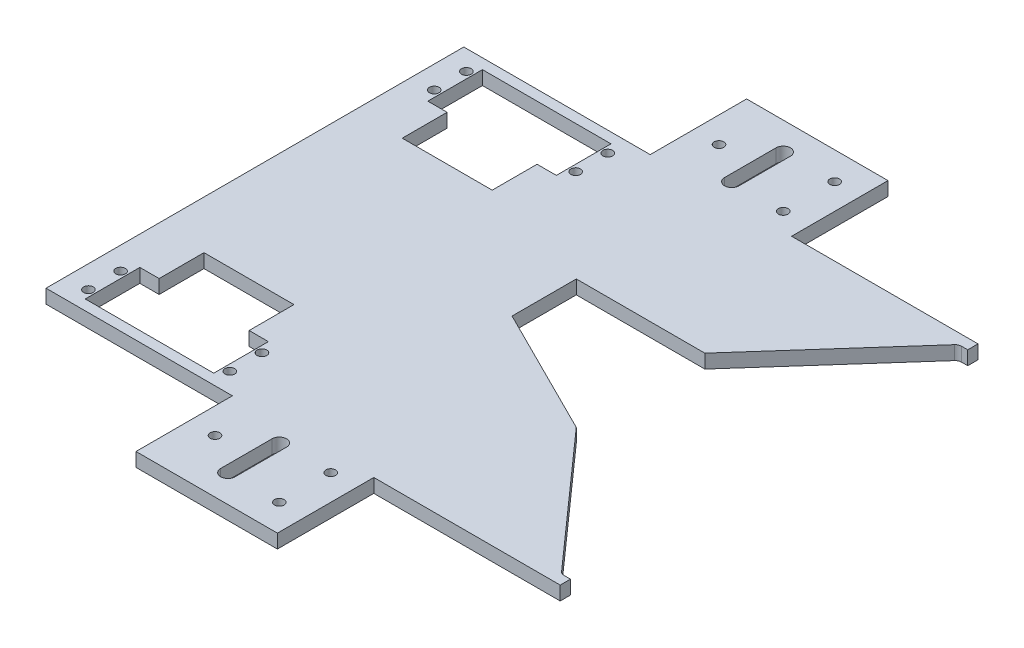
SolidWorks part; units mm, degrees
ref_plane "Front Plane" through (0, 0, 0) normal (0, 0, 1) x (1, 0, 0)
ref_plane "Top Plane" through (0, 0, 0) normal (0, 1, 0) x (1, 0, 0)
ref_plane "Right Plane" through (0, 0, 0) normal (1, 0, 0) x (0, 0, -1)
sketch "Sketch2" plane through (0, 0, 0) normal (0, 1, 0) x (1, 0, 0)
  line L2 (0, 0) -> (0, 65)
  line L3 (0, 65) -> (58, 65)
  line L4 (160, 0) -> (160, 65)
  line L8 (0, 0) -> (160, 0)
  line L9 (102, 65) -> (160, 65)
  line L11 (102, 65) -> (102, 95)
  line L12 (58, 65) -> (58, 95)
  line L13 (58, 95) -> (102, 95)
  dimension "D1" = 65
  dimension "D2" = 160
  dimension "D3" = 44
  dimension "D4" = 30
extrude "Boss-Extrude1" add sketch "Sketch2" along normal blind 4.3
mirror "Mirror1" about plane through (0, 4.3, 0) normal (0, 0, -1) of bodies 101
sketch "Sketch3" plane through (0, 4.3, 0) normal (0, 1, 0) x (1, 0, 0)
  line L0 (160, 61.8) -> (160, -61.8)
  line L1 (120.0126, 20) -> (157.1565, 61.8)
  line L3 (80.0126, 0) -> (80.0126, 20)
  line L4 (80.0126, 20) -> (120.0126, 20)
  line L12 (160, 65) -> (102, 65)
  line L13 (102, 65) -> (102, 95)
  line L15 (102, 95) -> (58, 95)
  line L16 (58, 65) -> (0, 65)
  line L17 (0, 65) -> (0, -65)
  line L18 (0, -65) -> (58, -65)
  line L20 (58, 95) -> (58, 65)
  line L22 (102, -65) -> (160, -65)
  line L23 (160, -65) -> (160, 65)
  line L36 (58, -65) -> (58, -95)
  line L38 (58, -95) -> (102, -95)
  line L39 (58, -95) -> (102, -95)
  line L40 (102, -95) -> (102, -65)
  line L42 (160, -61.8) -> (157.1556, -61.8)
  line L45 (160, 61.8) -> (157.1565, 61.8)
  line L48 (80.0126, 0) -> (120, -20)
  line L49 (120, -20) -> (157.1556, -61.8)
  line M24 (160, -65) -> (160, 65)
  dimension "D2" = 130
  dimension "D3" = 20
  dimension "D4" = 40
  dimension "D1" = 0
extrude "Cut-Extrude1" cut sketch "Sketch3" against normal blind 4.5 contours L48 L49 L1 L4 L3 M24 region at (132.7054, 4.3, -1.1594)
fillet "Fillet1" radius 2 2 edges at (157.1565, 2.15, -61.8) (157.1556, 2.15, 61.8)
ref_axis "Axis1" through (80, 4.3, 95) along (0, 0, -1)
sketch "Sketch4" plane through (0, 4.3, 0) normal (0, 1, 0) x (1, 0, 0)
  line L0 (80, -95) -> (80, 95)
  line L1 (102, -95) -> (58, -95) construction
  line L2 (102, 95) -> (58, 95) construction
ref_plane "Plane2" through (0, 4.3, 0) normal (0, 1, 0) x (1, 0, 0)
sketch "Sketch6" plane through (0, 4.3, 0) normal (0, 1, 0) x (1, 0, 0)
  line L3 (9, -61.8) -> (49, -61.8)
  line L6 (29, -45.8) -> (29, -44.8)
  line L7 (9, -44.8) -> (15, -44.8)
  line L11 (43, -44.8) -> (43, -30.8418)
  line L12 (15, -44.8) -> (15, -30.8418)
  line L13 (15, -30.8418) -> (43, -30.8418)
  line L15 (0, 0) -> (80.0126, 0)
  line L16 (80.0126, 0) -> (120, -20) construction
  line L18 (9, 44.8) -> (15, 44.8)
  line L20 (15, 30.8418) -> (43, 30.8418)
  line L21 (15, 44.8) -> (15, 30.8418)
  line L22 (43, 44.8) -> (43, 30.8418)
  line L25 (15, -45.8) -> (15, -30.8418) construction
  line L27 (9, 61.8) -> (49, 61.8)
  line L30 (4, -61.8) -> (3, -61.8)
  line L31 (0, -61.8) -> (160, -61.8) construction
  line L32 (3, -61.8) -> (4, -61.8)
  line L33 (3, -44.8) -> (3, -62.8) construction
  line L34 (3, -62.8) -> (55, -62.8) construction
  line L35 (55, -44.8) -> (55, -62.8) construction
  line L36 (4, -61.8) -> (54, -61.8) construction
  line L37 (0, 61.8) -> (160, 61.8) construction
  line L38 (54, 61.8) -> (55, 61.8)
  line L39 (54, 61.8) -> (55, 61.8)
  line L40 (43, 44.8) -> (49, 44.8)
  line L41 (4, -45.8) -> (4, -61.8) construction
  line L42 (4, -45.8) -> (54, -45.8) construction
  line L43 (43, -44.8) -> (49, -44.8)
  line L44 (3, -44.8) -> (55, -44.8) construction
  line L45 (29, -45.8) -> (29, -30.8418) construction
  line L46 (43, -45.8) -> (43, -30.8418) construction
  line L47 (54, -45.8) -> (54, -61.8) construction
  line L48 (9, -61.8) -> (49, -61.8)
  line L52 (9, 61.8) -> (9, 44.8)
  line L53 (55, 61.8) -> (54, 61.8)
  line L56 (49, 61.8) -> (49, 44.8)
  line L59 (3, -61.8) -> (4, -61.8)
  line L60 (9, -44.8) -> (9, -61.8)
  line L64 (49, -44.8) -> (49, -61.8)
  dimension "D4" = 1
  dimension "D5" = 14
  dimension "D6" = 14
extrude "Cut-Extrude2" cut sketch "Sketch6" against normal blind 10
sketch "Sketch7" plane through (0, 4.3, 0) normal (0, 1, 0) x (1, 0, 0)
  line L0 (0, 0) -> (80.0126, 0)
  line L1 (0, 65) -> (0, -65) construction
sketch "Sketch8" plane through (0, 4.3, 0) normal (0, 1, 0) x (1, 0, 0)
  circle A0 centre (7, 58.8) radius 1.5
  circle A1 centre (7, 48.8) radius 1.5
  circle A2 centre (51, 48.8) radius 1.5
  circle A3 centre (51, 58.8) radius 1.5
  circle A4 centre (7, -48.8) radius 1.5
  circle A5 centre (7, -58.8) radius 1.5
  circle A6 centre (51, -58.8) radius 1.5
  circle A7 centre (51, -48.8) radius 1.5
  dimension "D7" = 3
extrude "Cut-Extrude3" cut sketch "Sketch8" against normal blind 10
sketch "Sketch9" plane through (0, 0, 0) normal (0, -1, 0) x (1, 0, 0)
  line L0 (75.75, 70.4) -> (75.75, 86.4)
  line L1 (75.75, -86.4) -> (75.75, -70.4)
  line L2 (80.25, -86.4) -> (80.25, -70.4)
  line L4 (80.25, 70.4) -> (80.25, 86.4)
  circle A0 centre (94, 70.4) radius 1.5
  circle A1 centre (66, 78.4) radius 1.5
  circle A2 centre (66, -78.4) radius 1.5
  circle A3 centre (94, -86.4) radius 1.5
  circle A4 centre (94, 86.4) radius 1.5
  circle A5 centre (94, -70.4) radius 1.5
  arc A6 (75.75, -86.4) -> (80.25, -86.4) centre (78, -86.4) ccw
  arc A7 (80.25, -70.4) -> (75.75, -70.4) centre (78, -70.4) ccw
  arc A10 (75.75, 70.4) -> (80.25, 70.4) centre (78, 70.4) ccw
  arc A12 (80.25, 86.4) -> (75.75, 86.4) centre (78, 86.4) ccw
  dimension "D1" = 3
extrude "Cut-Extrude4" cut sketch "Sketch9" against normal blind 10
